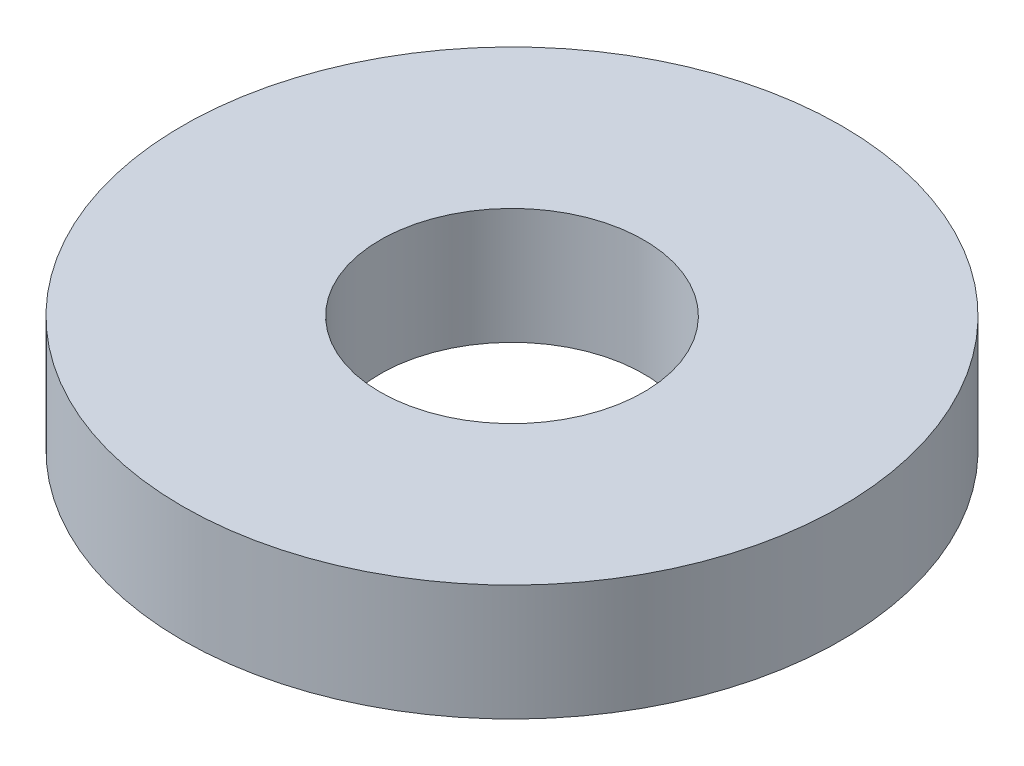
SolidWorks part; units mm, degrees
ref_plane "Front Plane" through (0, 0, 0) normal (0, 0, 1) x (1, 0, 0)
ref_plane "Top Plane" through (0, 0, 0) normal (0, 1, 0) x (1, 0, 0)
ref_plane "Right Plane" through (0, 0, 0) normal (1, 0, 0) x (0, 0, -1)
sketch "Sketch1" plane through (0, 0, 0) normal (0, 1, 0) x (1, 0, 0)
  circle A0 centre (0, 0) radius 62.5
  dimension "FLANGE_OD" = 125
extrude "Boss-Extrude1" add sketch "Sketch1" along normal blind 22
sketch "Sketch2" plane through (0, 0, 0) normal (0, 1, 0) x (1, 0, 0)
  circle A0 centre (0, 0) radius 25
  dimension "BORE_D" = 50
extrude "Cut-Extrude1" cut sketch "Sketch2" along normal through all
sketch "Sketch3" plane through (0, 22, 0) normal (0, 1, 0) x (1, 0, 0)
  circle A0 centre (0, 0) radius 19.2368 construction
  circle A1 centre (-19.2368, 0) radius 4.2614
  dimension "BOLT_D" = 8.5227
  dimension "BOLT_PCD" = 38.4736
extrude "Cut-Extrude2" cut sketch "Sketch3" against normal blind 17.9243 rebuild error yes
pattern_circular "CirPattern1" count 8 over 360 rebuild error yes
